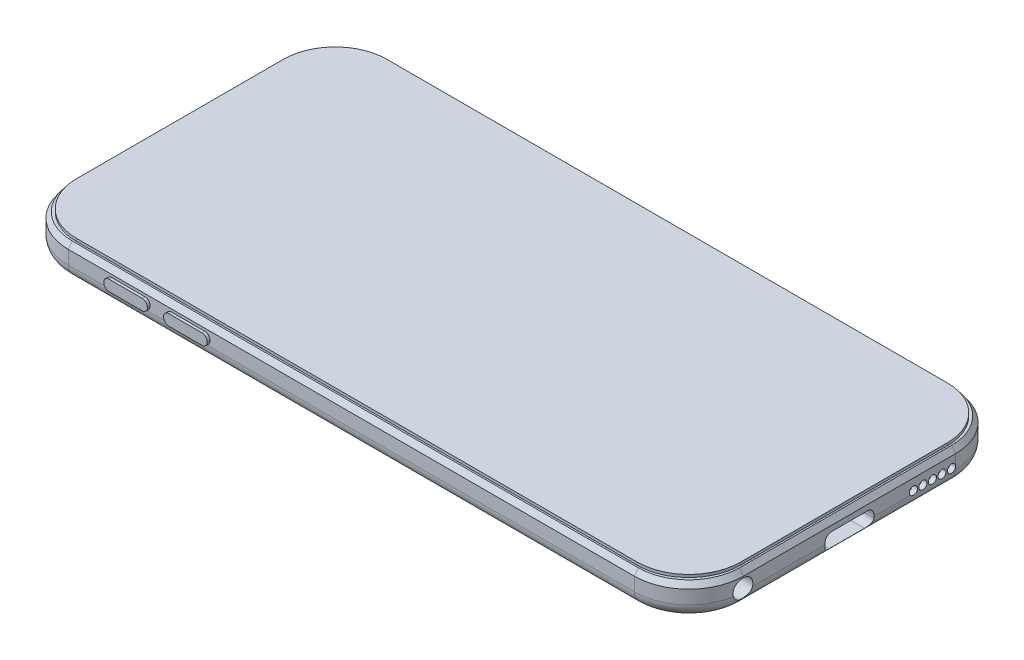
SolidWorks part; units mm, degrees
ref_plane "Front Plane" through (0, 0, 0) normal (0, 0, 1) x (1, 0, 0)
ref_plane "Top Plane" through (0, 0, 0) normal (0, 1, 0) x (1, 0, 0)
ref_plane "Right Plane" through (0, 0, 0) normal (1, 0, 0) x (0, 0, -1)
sketch "Sketch1" plane through (0, 0, 0) normal (0, 1, 0) x (1, 0, 0)
  line L0 (-62, 29.5) -> (62, -29.5) construction
  line L1 (-52, 29.5) -> (52, 29.5)
  line L2 (-62, 19.5) -> (-62, -19.5)
  line L3 (-52, -29.5) -> (52, -29.5)
  line L4 (62, 19.5) -> (62, -19.5)
  arc A0 (52, 29.5) -> (62, 19.5) centre (52, 19.5) cw
  arc A1 (52, -29.5) -> (62, -19.5) centre (52, -19.5) ccw
  arc A2 (-52, 29.5) -> (-62, 19.5) centre (-52, 19.5) ccw
  arc A3 (-62, -19.5) -> (-52, -29.5) centre (-52, -19.5) ccw
  point P7 (62, 29.5)
  point P16 (-62, -29.5)
  dimension "D3" = 10
  dimension "D1" = 124
  dimension "D2" = 59
extrude "Body" add sketch "Sketch1" along normal blind 6
fillet "Body Fillet" radius 2.5 8 edges at (0, 0, -29.5) (-59.0711, 0, -26.5711) (-62, 0, 0) (-59.0711, 0, 26.5711) (0, 0, 29.5) (59.0711, 0, 26.5711) (62, 0, 0) (59.0711, 0, -26.5711)
chamfer "Body Chamfer" distance 1 angle 35 8 edges at (-59.0711, 6, -26.5711) (-62, 6, 0) (-59.0711, 6, 26.5711) (0, 6, 29.5) (59.0711, 6, 26.5711) (62, 6, 0) (59.0711, 6, -26.5711) (0, 6, -29.5) first distance on face at (-58.0355, 4.25, -25.5355) first distance on face at (-62, 4.25, 0) first distance on face at (-58.0355, 4.25, 25.5355) first distance on face at (0, 4.25, 29.5) first distance on face at (58.0355, 4.25, 25.5355) first distance on face at (62, 4.25, 0) first distance on face at (58.0355, 4.25, -25.5355) first distance on face at (0, 4.25, -29.5)
sketch "Sketch2" plane through (0, 6, 0) normal (0, 1, 0) x (1, 0, 0)
  line L0 (-61.2998, 19.5) -> (-61.2998, -19.5) construction
  line L1 (-54.2998, 28.5109) -> (-54.2998, -28.5109) construction
  circle A0 centre (-54.2998, 0) radius 0.5
  arc A1 (-52, 28.7998) -> (-61.2998, 19.5) centre (-52, 19.5) ccw construction
  arc A2 (-61.2998, -19.5) -> (-52, -28.7998) centre (-52, -19.5) ccw construction
  dimension "D1" = 1
  dimension "D2" = 7
extrude "Front Camera Hole" cut sketch "Sketch2" against normal blind 0.5
chamfer "Front Camera Chamfer" distance 0.5 angle 35 1 edges at (-54.2998, 6, 0.5) first distance on face at (-54.2998, 6, 0.5)
sketch "Sketch3" plane through (0, 6, 0) normal (0, 1, 0) x (1, 0, 0)
  line L0 (-52, -28.7998) -> (52, -28.7998) construction
  line L1 (-45.2998, 25.2002) -> (44.7002, 25.2002)
  line L2 (-45.2998, 25.2002) -> (-45.2998, -25.7998)
  line L3 (-45.2998, -25.7998) -> (44.7002, -25.7998)
  line L4 (44.7002, 25.2002) -> (44.7002, -25.7998)
  line L7 (-61.2998, 19.5) -> (-61.2998, -19.5) construction
  dimension "D1" = 51
  dimension "D2" = 90
  dimension "D3" = 3
  dimension "D4" = 16
extrude "LCD" cut sketch "Sketch3" against normal blind 0.1
sketch "Sketch11" plane through (-62, 0, 0) normal (-1, 0, 0) x (0, 0, 1)
  line L0 (19.5, 5) -> (-19.5, 5) construction
  line L1 (-19.55, 4.5) -> (-12.45, 4.5)
  line L2 (-20.5, 3.55) -> (-20.5, 3.45)
  line L3 (-19.55, 2.5) -> (-12.45, 2.5)
  line L4 (-11.5, 3.55) -> (-11.5, 3.45)
  line L5 (-29.5, 5) -> (-29.5, 2.5) construction
  arc A0 (-12.45, 2.5) -> (-11.5, 3.45) centre (-12.45, 3.45) ccw
  arc A1 (-12.45, 4.5) -> (-11.5, 3.55) centre (-12.45, 3.55) cw
  arc A2 (-19.55, 4.5) -> (-20.5, 3.55) centre (-19.55, 3.55) ccw
  arc A3 (-20.5, 3.45) -> (-19.55, 2.5) centre (-19.55, 3.45) ccw
  point P6 (-11.5, 2.5)
  point P11 (-20.5, 4.5)
  point P14 (-20.5, 2.5)
  point P17 (-29.5, 3.75)
  dimension "D3" = 0.95
  dimension "D1" = 2
  dimension "D2" = 9
  dimension "D4" = 2.5
  dimension "D5" = 18
extrude "Power Button" add sketch "Sketch11" along normal mid plane 1
sketch "Sketch4" plane through (0, 6, 0) normal (0, 1, 0) x (1, 0, 0)
  line L1 (51.5, -28.5) -> (-51.5, -28.5)
  line L2 (61, -19) -> (61, 19)
  line L3 (51.5, 28.5) -> (-51.5, 28.5)
  line L6 (-61, -19) -> (-61, 19)
  line L7 (61, -28.5) -> (-61, 28.5) construction
  line L8 (61, 28.5) -> (-61, -28.5) construction
  arc A0 (61, 19) -> (51.5, 28.5) centre (51.5, 19) ccw
  arc A1 (51.5, -28.5) -> (61, -19) centre (51.5, -19) ccw
  arc A2 (-51.5, -28.5) -> (-61, -19) centre (-51.5, -19) cw
  arc A3 (-51.5, 28.5) -> (-61, 19) centre (-51.5, 19) ccw
  point P0 (0, 0)
  dimension "D2" = 38
  dimension "D3" = 103
  dimension "D1" = 9.5
extrude "Glass Screen" add sketch "Sketch4" along normal blind 0.5 separate body
sketch "Sketch5" plane through (0, 0, 29.5) normal (0, 0, 1) x (1, 0, 0)
  line L0 (-52, 2.5) -> (52, 2.5) construction
  line L1 (-37.95, 4.5) -> (-44.05, 4.5)
  line L2 (-37, 3.55) -> (-37, 3.45)
  line L3 (-37.95, 2.5) -> (-44.05, 2.5)
  line L4 (-45, 3.55) -> (-45, 3.45)
  line L5 (-37, 4.5) -> (-45, 2.5) construction
  line L6 (-37, 2.5) -> (-45, 4.5) construction
  line L7 (-62, 5) -> (-62, 2.5) construction
  line L9 (-33.05, 4.5) -> (-26.95, 4.5)
  line L10 (-34, 3.55) -> (-34, 3.45)
  line L11 (-33.05, 2.5) -> (-26.95, 2.5)
  line L12 (-26, 3.55) -> (-26, 3.45)
  arc A0 (-44.05, 2.5) -> (-45, 3.45) centre (-44.05, 3.45) cw
  arc A1 (-44.05, 4.5) -> (-45, 3.55) centre (-44.05, 3.55) ccw
  arc A2 (-37, 3.45) -> (-37.95, 2.5) centre (-37.95, 3.45) cw
  arc A3 (-37.95, 4.5) -> (-37, 3.55) centre (-37.95, 3.55) cw
  arc A4 (-26.95, 2.5) -> (-26, 3.45) centre (-26.95, 3.45) ccw
  arc A5 (-26.95, 4.5) -> (-26, 3.55) centre (-26.95, 3.55) cw
  arc A6 (-34, 3.45) -> (-33.05, 2.5) centre (-33.05, 3.45) ccw
  arc A7 (-33.05, 4.5) -> (-34, 3.55) centre (-33.05, 3.55) ccw
  point P0 (-42.0295, 3.5)
  point P27 (-26, 2.5)
  point P30 (-26, 4.5)
  point P35 (-34, 4.5)
  dimension "D3" = 0.95
  dimension "D4" = 0.95
  dimension "D8" = 0.95
  dimension "D1" = 2
  dimension "D2" = 8
  dimension "D5" = 17
  dimension "D6" = 8
  dimension "D7" = 2
  dimension "D9" = 3
extrude "Volume Buttons" add sketch "Sketch5" along normal blind 0.5
sketch "Sketch7" plane through (0, 6, 0) normal (0, 1, 0) x (1, 0, 0)
  line L0 (44.7002, -25.7998) -> (44.7002, 25.2002) construction
  circle A0 centre (52.7002, 0) radius 5
  point P2 (44.7002, -0.2998)
  dimension "D1" = 10
  dimension "D2" = 8
extrude "Home Button Hole" cut sketch "Sketch7" against normal blind 0.5
sketch "Sketch8" plane through (0, 5.5, 0) normal (0, 1, 0) x (1, 0, 0)
  circle A0 centre (52.7002, 0) radius 4.875
  dimension "D1" = 9.75
extrude "Boss-Extrude4" add sketch "Sketch8" along normal blind 1 separate body
sketch "Sketch10" plane through (0, 6.5, 0) normal (0, 1, 0) x (1, 0, 0)
  line L0 (50.9502, 1.25) -> (50.9502, -1.25)
  line L1 (51.4502, 2) -> (53.9502, 2)
  line L2 (50.7002, 1.25) -> (50.7002, -1.25)
  line L3 (51.4502, -2) -> (53.9502, -2)
  line L4 (54.7002, 1.25) -> (54.7002, -1.25)
  line L5 (50.7002, 2) -> (54.7002, -2) construction
  line L6 (50.7002, -2) -> (54.7002, 2) construction
  line L7 (51.4502, -1.75) -> (53.9502, -1.75)
  line L8 (54.4502, 1.25) -> (54.4502, -1.25)
  line L9 (51.4502, 1.75) -> (53.9502, 1.75)
  arc A0 (53.9502, 2) -> (54.7002, 1.25) centre (53.9502, 1.25) cw
  arc A1 (53.9502, -2) -> (54.7002, -1.25) centre (53.9502, -1.25) ccw
  arc A2 (50.7002, -1.25) -> (51.4502, -2) centre (51.4502, -1.25) ccw
  arc A3 (51.4502, 2) -> (50.7002, 1.25) centre (51.4502, 1.25) ccw
  arc A4 (51.4502, 1.75) -> (50.9502, 1.25) centre (51.4502, 1.25) ccw
  arc A5 (50.9502, -1.25) -> (51.4502, -1.75) centre (51.4502, -1.25) ccw
  arc A6 (53.9502, -1.75) -> (54.4502, -1.25) centre (53.9502, -1.25) ccw
  arc A7 (53.9502, 1.75) -> (54.4502, 1.25) centre (53.9502, 1.25) cw
  point P0 (52.7002, 0)
  dimension "D3" = 0.75
  dimension "D1" = 4
  dimension "D2" = 4
  dimension "D4" = 0.25
extrude "Cut-Extrude4" cut sketch "Sketch10" against normal blind 0.001
sketch "Sketch13" plane through (62, 0, 0) normal (1, 0, 0) x (0, 0, -1)
  circle A0 centre (-19.5, 3) radius 1.75
extrude "3.5mm Headphone Jack" cut sketch "Sketch13" against normal blind 14
sketch "Sketch15" plane through (62, 0, 0) normal (1, 0, 0) x (0, 0, -1)
  line L0 (-19.5, 6) -> (19.5, 6) construction
  circle A0 centre (18.75, 3) radius 0.75
  circle A1 centre (17, 3) radius 0.75
  circle A2 centre (15.25, 3) radius 0.75
  circle A3 centre (13.5, 3) radius 0.75
  circle A4 centre (11.75, 3) radius 0.75
  dimension "D1" = 1.5
  dimension "D2" = 10.75
  dimension "D4" = 3
  dimension "D3" = 5
extrude "Speaker Holes" cut sketch "Sketch15" against normal blind 1
sketch "Sketch16" plane through (62, 0, 0) normal (1, 0, 0) x (0, 0, -1)
  line L1 (-3.25, 4) -> (3.25, 4)
  line L2 (-4.5, 2.75) -> (-4.5, 2.25)
  line L3 (-3.25, 1) -> (3.25, 1)
  line L4 (4.5, 2.75) -> (4.5, 2.25)
  line L6 (-19.5, 6) -> (19.5, 6) construction
  arc A0 (3.25, 4) -> (4.5, 2.75) centre (3.25, 2.75) cw
  arc A1 (3.25, 1) -> (4.5, 2.25) centre (3.25, 2.25) ccw
  arc A2 (-4.5, 2.25) -> (-3.25, 1) centre (-3.25, 2.25) ccw
  arc A3 (-3.25, 4) -> (-4.5, 2.75) centre (-3.25, 2.75) ccw
  point P8 (4.5, 1)
  point P11 (-4.5, 1)
  point P14 (-4.5, 4)
  dimension "D3" = 1.25
  dimension "D1" = 3
  dimension "D2" = 9
  dimension "D4" = 25
  dimension "D5" = 2
extrude "Charger Socket" cut sketch "Sketch16" against normal blind 4
sketch "Sketch17" plane through (58, 0, 0) normal (1, 0, 0) x (0, 0, -1)
  line L1 (-3.25, 4.0485) -> (3.25, 4.0485)
  line L2 (-4.5, 2.7985) -> (-4.5, 2.2015)
  line L3 (-3.25, 0.9515) -> (3.25, 0.9515)
  line L4 (4.5, 2.7985) -> (4.5, 2.2015)
  line L5 (-4.5, 4.0485) -> (4.5, 0.9515) construction
  line L6 (-4.5, 0.9515) -> (4.5, 4.0485) construction
  line L10 (-4.4, 2.7985) -> (-4.4, 2.2015)
  line L11 (-3.25, 1.0515) -> (3.25, 1.0515)
  line L12 (4.4, 2.7985) -> (4.4, 2.2015)
  line L13 (-3.25, 3.9485) -> (3.25, 3.9485)
  arc A0 (3.25, 0.9515) -> (4.5, 2.2015) centre (3.25, 2.2015) ccw
  arc A1 (3.25, 4.0485) -> (4.5, 2.7985) centre (3.25, 2.7985) cw
  arc A2 (-4.5, 2.2015) -> (-3.25, 0.9515) centre (-3.25, 2.2015) ccw
  arc A3 (-3.25, 4.0485) -> (-4.5, 2.7985) centre (-3.25, 2.7985) ccw
  arc A8 (-3.25, 3.9485) -> (-4.4, 2.7985) centre (-3.25, 2.7985) ccw
  arc A9 (-4.4, 2.2015) -> (-3.25, 1.0515) centre (-3.25, 2.2015) ccw
  arc A10 (3.25, 1.0515) -> (4.4, 2.2015) centre (3.25, 2.2015) ccw
  arc A11 (3.25, 3.9485) -> (4.4, 2.7985) centre (3.25, 2.7985) cw
  point P0 (0, 2.5)
  dimension "D1" = 1.25
  dimension "D3" = 0.1
sketch "Sketch18" plane through (0, 0, 0) normal (0, -1, 0) x (1, 0, 0)
  circle A0 centre (-51.9842, -21.5) radius 4
  dimension "D1" = 8
  dimension "D2" = 8
extrude "Outer Camera Ring" add sketch "Sketch18" along normal blind 0.5
sketch "Sketch19" plane through (0, -0.5, 0) normal (0, -1, 0) x (1, 0, 0)
  circle A0 centre (-51.9842, -21.5) radius 3.5
  dimension "D1" = 7
extrude "Camera Glass" cut sketch "Sketch19" against normal blind 0.5
sketch "Sketch20" plane through (0, 0, 0) normal (0, -1, 0) x (1, 0, 0)
  circle A0 centre (-51.9842, -21.5) radius 2
  dimension "D1" = 4
extrude "Inner Camera Ring" add sketch "Sketch20" along normal blind 0.2
sketch "Sketch21" plane through (0, -0.2, 0) normal (0, -1, 0) x (1, 0, 0)
  circle A0 centre (-51.9842, -21.5) radius 1
  dimension "D1" = 2
extrude "Iris" cut sketch "Sketch21" against normal blind 0.05
fillet "Iris fillet" radius 0.1 1 edges at (-51.9842, -0.2, -22.5)
sketch "Sketch22" plane through (0, -0.2, 0) normal (0, -1, 0) x (1, 0, 0)
  circle A0 centre (-51.9842, -21.5) radius 3.5
  circle A1 centre (-51.9842, -21.5) radius 2
extrude "Thick Ring" add sketch "Sketch22" along normal blind 0.1 separate body
ref_plane "Plane1" through (0, -0.45, 0) normal (0, -1, 0) x (-1, 0, 0)
sketch "Sketch23" plane through (0, -0.45, 0) normal (0, -1, 0) x (-1, 0, 0)
  circle A0 centre (51.9842, 21.5) radius 3.5
extrude "Camera Base" add sketch "Sketch23" against normal blind 0.1
sketch "Sketch24" plane through (0, 0, 0) normal (0, -1, 0) x (1, 0, 0)
  line L0 (-51.9842, -49.2848) -> (-51.9842, 48.9609) construction
  line L2 (-52.2342, 23.4169) -> (-51.7342, 23.4169)
  line L3 (-55.4842, 20.1669) -> (-55.4842, 5.6669)
  line L4 (-52.2342, 2.4169) -> (-51.7342, 2.4169)
  line L5 (-48.4842, 20.1669) -> (-48.4842, 5.6669)
  line L6 (-55.4842, 23.4169) -> (-48.4842, 2.4169) construction
  line L7 (-55.4842, 2.4169) -> (-48.4842, 23.4169) construction
  arc A0 (-55.4842, 5.6669) -> (-52.2342, 2.4169) centre (-52.2342, 5.6669) ccw
  arc A1 (-51.7342, 2.4169) -> (-48.4842, 5.6669) centre (-51.7342, 5.6669) ccw
  arc A2 (-51.7342, 23.4169) -> (-48.4842, 20.1669) centre (-51.7342, 20.1669) cw
  arc A3 (-52.2342, 23.4169) -> (-55.4842, 20.1669) centre (-52.2342, 20.1669) ccw
  point P3 (-51.9842, 12.9169)
  dimension "D3" = 3.25
  dimension "D1" = 7
  dimension "D2" = 21
extrude "Rubber Finger Place" cut sketch "Sketch24" against normal blind 0.001
sketch "Sketch25" plane through (0, 0, 0) normal (0, -1, 0) x (1, 0, 0)
  line L0 (-76.6633, -21.5) -> (69.3665, -21.5) construction
  line L1 (59.5, -19.5) -> (59.5, 19.5) construction
  circle A0 centre (53.5, -21.5) radius 4
  dimension "D1" = 8
  dimension "D2" = 6
extrude "Strap Hole" cut sketch "Sketch25" against normal blind 1
sketch "Sketch26" plane through (0, 1, 0) normal (0, -1, 0) x (1, 0, 0)
  circle A0 centre (53.5, -21.5) radius 3.95
extrude "Strap Ring" add sketch "Sketch26" along normal blind 1
sketch "Sketch27" plane through (0, 0, 0) normal (0, -1, 0) x (1, 0, 0)
  line L0 (-51.9842, -21.5) -> (-51.9842, 2.4169) construction
  line L1 (-52.2342, 2.4169) -> (-51.7342, 2.4169) construction
  circle A0 centre (-51.9842, -12.4504) radius 2
  dimension "D1" = 4
extrude "Cut-Extrude12" cut sketch "Sketch27" against normal blind 1.5
sketch "Sketch28" plane through (0, 1.5, 0) normal (0, -1, 0) x (1, 0, 0)
  circle A0 centre (-51.9842, -12.4504) radius 2
  circle A1 centre (-51.9842, -12.4504) radius 1.5
  dimension "D1" = 3
  dimension "D2" = 4
extrude "Boss-Extrude17" add sketch "Sketch28" along normal blind 1.5
sketch "Sketch29" plane through (0, 0, 0) normal (0, -1, 0) x (1, 0, 0)
  line L0 (-51.9842, -12.4504) -> (-51.9842, -21.5) construction
  line L1 (-51.9842, -15.04) -> (-51.9842, -15.5509) construction
  line L2 (-51.7595, -15.04) -> (-51.7595, -15.5509)
  line L3 (-52.2088, -15.04) -> (-52.2088, -15.5509)
  arc A0 (-51.7595, -15.04) -> (-52.2088, -15.04) centre (-51.9842, -15.04) ccw
  arc A1 (-52.2088, -15.5509) -> (-51.7595, -15.5509) centre (-51.9842, -15.5509) ccw
  point P6 (-51.9842, -15.2955)
extrude "Mic" cut sketch "Sketch29" against normal blind 0.5
chamfer "Mic Chamfer" distance 0.075 angle 45 4 edges at (-51.9842, 0, -15.7756) (-51.7595, 0, -15.2955) (-52.2088, 0, -15.2955) (-51.9842, 0, -14.8154)
ref_plane "Plane2" through (0, 0.075, 0) normal (0, -1, 0) x (-1, 0, 0)
sketch "Sketch30" plane through (0, 0.075, 0) normal (0, -1, 0) x (-1, 0, 0)
  line L0 (51.9842, 15.5509) -> (51.9842, 15.04) construction
  line L1 (52.2081, 15.5509) -> (52.2081, 15.04)
  line L2 (51.7603, 15.5509) -> (51.7603, 15.04)
  arc A0 (52.2081, 15.5509) -> (51.7603, 15.5509) centre (51.9842, 15.5509) ccw
  arc A1 (51.7603, 15.04) -> (52.2081, 15.04) centre (51.9842, 15.04) ccw
  point P4 (51.9842, 15.2955)
extrude "Mic Mesh" add sketch "Sketch30" against normal blind 0.05 separate body
sketch "Sketch31" plane through (0, 5.5, 0) normal (0, 1, 0) x (1, 0, 0)
  circle A0 centre (52.7002, 0) radius 4.8604
sketch "Sketch32" plane through (0, 5.5, 0) normal (0, 1, 0) x (1, 0, 0)
  circle A0 centre (52.7002, 0) radius 4.8599
extrude "Home Button" add sketch "Sketch32" along normal blind 0.49
sketch "Sketch33" plane through (0, 5.99, 0) normal (0, 1, 0) x (1, 0, 0)
  line L0 (50.7002, 1.5) -> (50.7002, -1.5)
  line L1 (51.2002, 2.5) -> (54.2002, 2.5)
  line L2 (50.2002, 1.5) -> (50.2002, -1.5)
  line L3 (51.2002, -2.5) -> (54.2002, -2.5)
  line L4 (55.2002, 1.5) -> (55.2002, -1.5)
  line L5 (50.2002, 2.5) -> (55.2002, -2.5) construction
  line L6 (50.2002, -2.5) -> (55.2002, 2.5) construction
  line L7 (51.2002, -2) -> (54.2002, -2)
  line L8 (54.7002, 1.5) -> (54.7002, -1.5)
  line L9 (51.2002, 2) -> (54.2002, 2)
  arc A0 (51.2002, -2.5) -> (50.2002, -1.5) centre (51.2002, -1.5) cw
  arc A1 (54.2002, -2.5) -> (55.2002, -1.5) centre (54.2002, -1.5) ccw
  arc A2 (54.2002, 2.5) -> (55.2002, 1.5) centre (54.2002, 1.5) cw
  arc A3 (51.2002, 2.5) -> (50.2002, 1.5) centre (51.2002, 1.5) ccw
  arc A4 (51.2002, 2) -> (50.7002, 1.5) centre (51.2002, 1.5) ccw
  arc A5 (51.2002, -2) -> (50.7002, -1.5) centre (51.2002, -1.5) cw
  arc A6 (54.2002, -2) -> (54.7002, -1.5) centre (54.2002, -1.5) ccw
  arc A7 (54.2002, 2) -> (54.7002, 1.5) centre (54.2002, 1.5) cw
  point P0 (52.7002, 0)
  dimension "D3" = 1
  dimension "D1" = 5
  dimension "D2" = 5
  dimension "D4" = 0.5
extrude "Home sq" [suppressed] add sketch "Sketch33" along normal blind 0.0001
